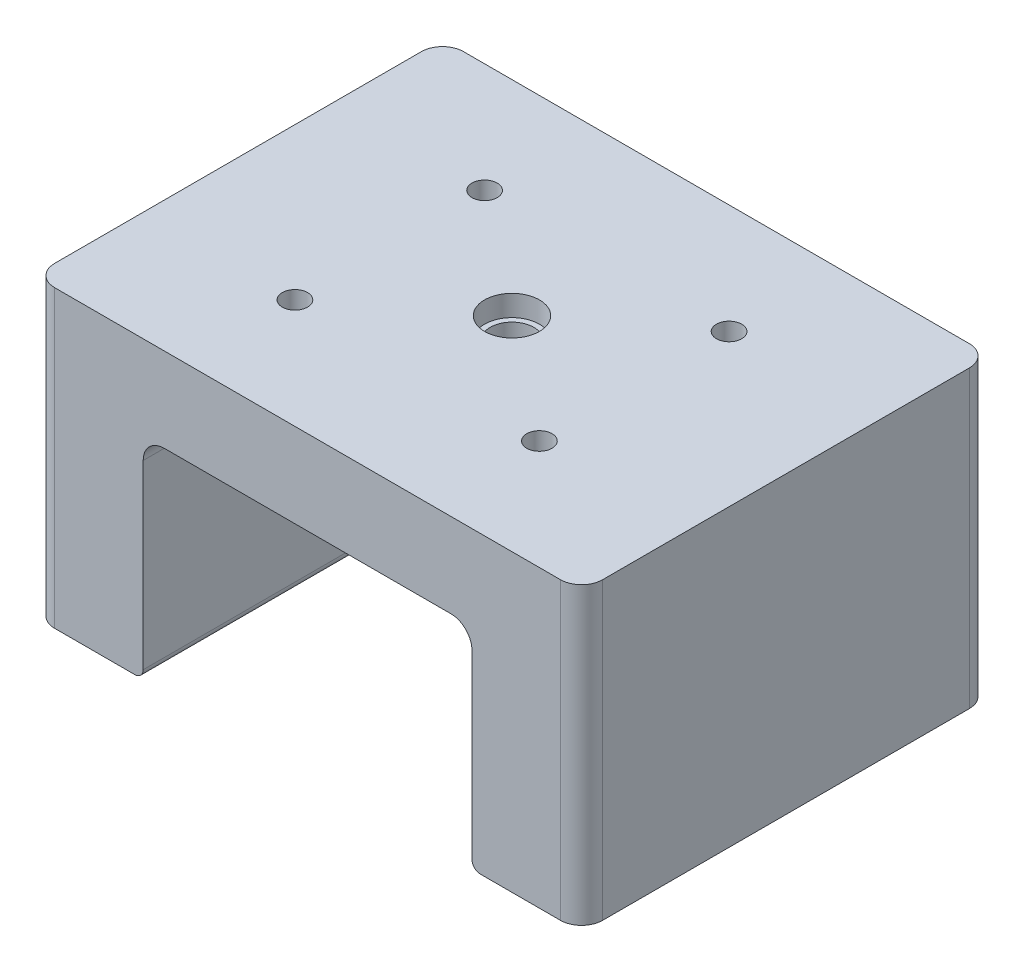
SolidWorks part; units mm, degrees
material "K110"
ref_plane "Front Plane" through (0, 0, 0) normal (0, 0, 1) x (1, 0, 0)
ref_plane "Top Plane" through (0, 0, 0) normal (0, 1, 0) x (1, 0, 0)
ref_plane "Right Plane" through (0, 0, 0) normal (1, 0, 0) x (0, 0, -1)
sketch "Sketch1" plane through (0, 0, 0) normal (0, 1, 0) x (1, 0, 0)
  line L0 (-65, -48.5) -> (-65, 48.5)
  line L7 (-65, 48.5) -> (65, 48.5)
  line L8 (65, -48.5) -> (65, 48.5)
  line L9 (-65, -48.5) -> (65, -48.5)
  point P0 (0, 0)
  point P10 (0, -48.5)
  point P11 (-65, 0)
  dimension "D3" = 97
  dimension "D4" = 130
extrude "Boss-Extrude1" add sketch "Sketch1" along normal blind 70
sketch "Sketch2" plane through (0, 0, 48.5) normal (0, 0, 1) x (1, 0, 0)
  line L0 (-65, 0) -> (65, 0) construction
  line L1 (-39, 0) -> (39, 0)
  line L2 (-39, 0) -> (-39, 50)
  line L3 (-39, 50) -> (39, 50)
  line L4 (39, 0) -> (39, 50)
  dimension "D1" = 78
  dimension "D2" = 50
extrude "Cut-Extrude1" cut sketch "Sketch2" against normal through all
fillet "Fillet3" radius 5 2 edges at (39, 50, 0) (-39, 50, 0)
sketch "Sketch3" plane through (0, 70, 0) normal (0, 1, 0) x (1, 0, 0)
  circle A0 centre (0, 0) radius 5.2
  dimension "D1" = 10.4
extrude "Cut-Extrude2" cut sketch "Sketch3" against normal through all
sketch "Sketch4" plane through (0, 70, 0) normal (0, 1, 0) x (1, 0, 0)
  circle A0 centre (0, 0) radius 6.5
  dimension "D1" = 13
extrude "Cut-Extrude3" cut sketch "Sketch4" against normal blind 5
fillet "Fillet2" radius 5 4 edges at (-65, 35, -48.5) (-65, 35, 48.5) (65, 35, -48.5) (65, 35, 48.5)
fillet "Fillet4" radius 2 2 edges at (39, 0, 0) (-39, 0, 0)
hole_wizard "Ø5.0 (5) Diameter Hole1" positions "Sketch7" profile "Sketch6" hole size "Ø5.0" standard "ISO" end condition through all
sketch "Sketch7" plane through (0, 70, 0) normal (0, 1, 0) x (1, 0, 0)
  point P0 (-29, 22.5)
  point P3 (29, 22.5)
  point P6 (29, -22.5)
  point P9 (-29, -22.5)
sketch "Sketch6" plane through (-29, 70, -22.5) normal (1, 0, 0) x (0, 0, 1)
  line L0 (0, 0) -> (0, 70)
  line L1 (0, 70) -> (3, 70)
  line L2 (3, 70) -> (3, 0)
  line L5 (3, 0) -> (0, 0)
  line L11 (0, -6.35) -> (0, 107.95) construction
  dimension "Thru Hole Dia." = 6
  dimension "Thru Hole Depth" = 70
